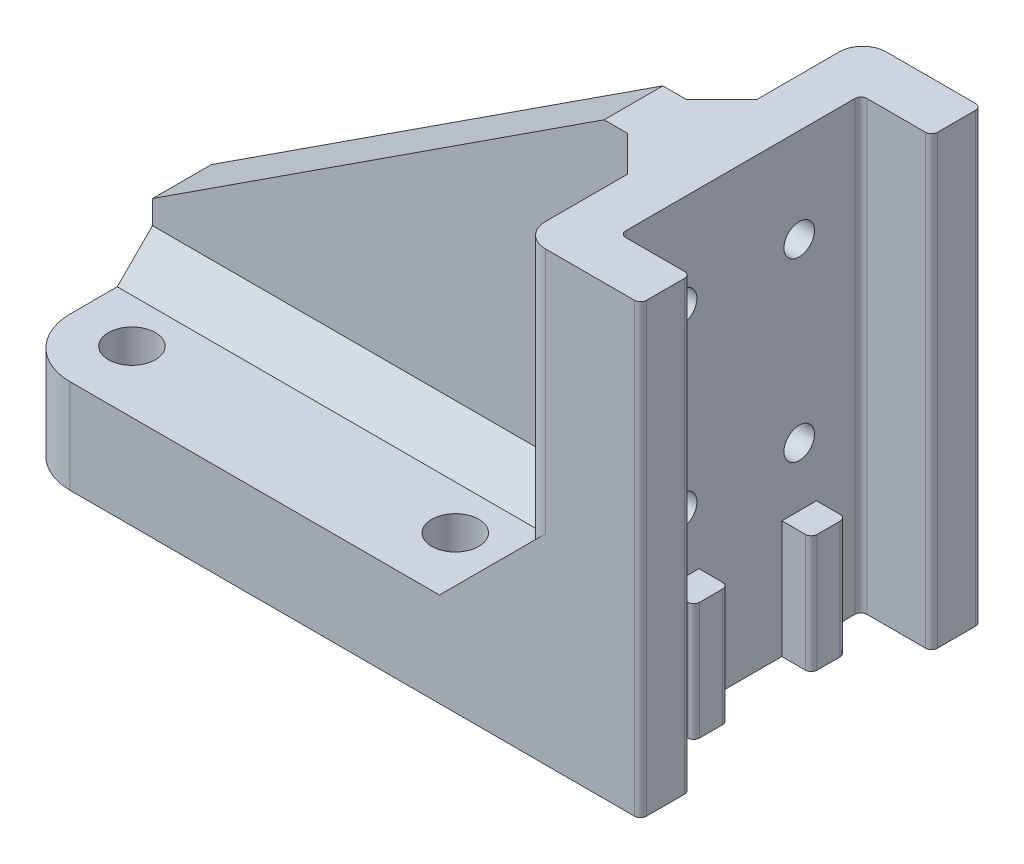
SolidWorks part; units mm, degrees
ref_plane "Plan de face" through (0, 0, 0) normal (0, 0, 1) x (1, 0, 0)
ref_plane "Plan de dessus" through (0, 0, 0) normal (0, 1, 0) x (1, 0, 0)
ref_plane "Plan de droite" through (0, 0, 0) normal (1, 0, 0) x (0, 0, -1)
sketch "Esquisse1" plane through (0, 0, 0) normal (0, 1, 0) x (1, 0, 0)
  line L0 (0, 29) -> (0, 0) construction
  line L1 (37.5, 29) -> (-37.5, 29)
  line L2 (37.5, 29) -> (37.5, -29)
  line L3 (37.5, -29) -> (-37.5, -29)
  line L4 (-37.5, 29) -> (-37.5, -29)
  line L5 (37.5, 29) -> (-37.5, -29) construction
  line L6 (37.5, -29) -> (-37.5, 29) construction
  line L7 (0, 0) -> (37.5, 0) construction
  circle A0 centre (-27.5, 18.5) radius 4
  circle A1 centre (27.5, 18.5) radius 4
  circle A2 centre (27.5, -18.5) radius 4
  circle A3 centre (-27.5, -18.5) radius 4
  point P0 (0, 0)
  dimension "D3" = 8
  dimension "D1" = 75
  dimension "D2" = 58
  dimension "D4" = 55
  dimension "D5" = 37
extrude "Boss.-Extru.1" add sketch "Esquisse1" along normal blind 16
sketch "Esquisse2" plane through (37.5, 0, 0) normal (1, 0, 0) x (0, 0, -1)
  line L4 (-29, 0) -> (29, 0)
  line L5 (29, 0) -> (29, 16)
  line L6 (29, 16) -> (-29, 16)
  line L7 (-29, 16) -> (-29, 0)
  line L8 (-29, 0) -> (29, 0)
  line L9 (29, 0) -> (29, 16)
  line L10 (29, 16) -> (-29, 16)
  line L11 (-29, 16) -> (-29, 0)
  dimension "D1" = 0
extrude "Boss.-Extru.2" add sketch "Esquisse2" along normal blind 20
sketch "Esquisse3" plane through (0, 16, 0) normal (0, 1, 0) x (1, 0, 0)
  line L0 (-37.5, -29) -> (57.5, -29) construction
  line L1 (57.5, 29) -> (49.3095, 29)
  line L2 (57.5, 29) -> (57.5, -29)
  line L3 (57.5, -29) -> (49.3095, -29)
  line L4 (49.3095, 29) -> (49.3095, -29)
extrude "Boss.-Extru.3" add sketch "Esquisse3" along normal blind 60
sketch "Esquisse4" plane through (57.5, 0, 0) normal (1, 0, 0) x (0, 0, -1)
  line L0 (0, 76) -> (0, 0) construction
  line L1 (-29, 76) -> (29, 76) construction
  line L2 (-29, 0) -> (29, 0) construction
  line L3 (20.5, 76) -> (20.5, 0)
  line L4 (-29, 76) -> (-20.5, 76)
  line L5 (-29, 76) -> (-29, 0)
  line L6 (-29, 0) -> (-20.5, 0)
  line L7 (-20.5, 76) -> (-20.5, 0)
  line L8 (29, 0) -> (20.5, 0)
  line L9 (29, 76) -> (29, 0)
  line L10 (29, 76) -> (20.5, 76)
  dimension "D1" = 41
extrude "Boss.-Extru.4" add sketch "Esquisse4" along normal blind 12
sketch "Esquisse5" plane through (57.5, 0, 0) normal (1, 0, 0) x (0, 0, -1)
  line L0 (0, 76) -> (0, 0) construction
  line L1 (-20.5, 76) -> (20.5, 76) construction
  line L2 (-20.5, 0) -> (20.5, 0) construction
  line L7 (-10, 20) -> (-10, -4.3804) construction
  line L8 (-12.95, 20) -> (-12.95, 0)
  line L9 (-7.05, 20) -> (-7.05, 0)
  line L10 (10, 20) -> (10, -4.3804) construction
  line L13 (7.05, 20) -> (7.05, 0)
  line L14 (12.95, 0) -> (7.05, 0)
  line L15 (12.95, 20) -> (12.95, 0)
  line L16 (12.95, 20) -> (7.05, 20)
  line L17 (-12.95, 20) -> (-7.05, 20)
  line L18 (-12.95, 0) -> (-7.05, 0)
  dimension "D1" = 5.9
  dimension "D2" = 20
  dimension "D3" = 20
extrude "Boss.-Extru.5" add sketch "Esquisse5" along normal blind 5
sketch "Esquisse6" plane through (49.3095, 0, 0) normal (-1, 0, 0) x (0, 0, 1)
  line L0 (0, 76) -> (0, 16) construction
  line L1 (-29, 76) -> (29, 76) construction
  line L2 (-29, 16) -> (29, 16) construction
  line L4 (5, 16) -> (-5, 16)
  line L5 (5, 16) -> (5, 76)
  line L6 (5, 76) -> (-5, 76)
  line L7 (-5, 16) -> (-5, 76)
  line L8 (5, 16) -> (-5, 76) construction
  line L9 (5, 76) -> (-5, 16) construction
  point P6 (0, 46)
  dimension "D1" = 10
extrude "Boss.-Extru.6" add sketch "Esquisse6" along normal up to surface (86.8095 mm away) up to face at (-37.5, 8, 0)
sketch "Esquisse7" plane through (49.3095, 0, 0) normal (-1, 0, 0) x (0, 0, 1)
  line L0 (-10, 76) -> (-10, 16) construction
  line L1 (-29, 76) -> (-5, 76) construction
  line L2 (-29, 16) -> (-5, 16) construction
  line L3 (0, 76) -> (0, 0) construction
  line L4 (-5, 76) -> (5, 76) construction
  line L5 (10, 76) -> (10, 16) construction
  circle A0 centre (-10, 60) radius 2.6
  circle A1 centre (-10, 30) radius 2.6
  circle A2 centre (10, 30) radius 2.6
  circle A3 centre (10, 60) radius 2.6
  dimension "D2" = 5.2
  dimension "D1" = 20
  dimension "D3" = 16
  dimension "D4" = 30
extrude "Enlèv. mat.-Extru.1" cut sketch "Esquisse7" against normal through all
sketch "Esquisse8" plane through (49.3095, 0, 0) normal (-1, 0, 0) x (0, 0, 1)
  circle A0 centre (-10, 60) radius 4.5
  circle A1 centre (-10, 30) radius 4.5
  circle A2 centre (10, 60) radius 4.5
  circle A3 centre (10, 30) radius 4.5
  dimension "D1" = 9
extrude "Enlèv. mat.-Extru.2" cut sketch "Esquisse8" against normal blind 3
sketch "Esquisse9" plane through (0, 0, -5) normal (0, 0, -1) x (-1, 0, 0)
  line L0 (-39.3095, 76) -> (37.5, 26)
  line L1 (37.5, 76) -> (-49.3095, 76) construction
  line L2 (37.5, 16) -> (37.5, 76) construction
  line L3 (37.5, 26) -> (37.5, 76)
  line L4 (37.5, 76) -> (-39.3095, 76)
  dimension "D1" = 10
  dimension "D2" = 10
extrude "Enlèv. mat.-Extru.3" cut sketch "Esquisse9" against normal through all
chamfer "Chanfrein1" distance 14 angle 45 2 edges at (49.3095, 16, 17) (49.3095, 16, -17)
chamfer "Chanfrein2" distance 6 angle 45 2 edges at (-1.0952, 16, 5) (-1.0952, 16, -5)
chamfer "Chanfrein3" distance 6 angle 45 2 edges at (49.3095, 53, 5) (49.3095, 53, -5)
fillet "Congé1" radius 10 2 edges at (-37.5, 8, 29) (-37.5, 8, -29)
fillet "Congé2" radius 4 2 edges at (49.3095, 53, 29) (49.3095, 53, -29)
fillet "Congé3" radius 1 4 edges at (69.5, 38, -29) (69.5, 38, -20.5) (69.5, 38, 20.5) (69.5, 38, 29)
fillet "Congé4" radius 1 6 edges at (57.5, 38, -20.5) (57.5, 38, 20.5) (62.5, 10, -12.95) (62.5, 10, -7.05) (62.5, 10, 7.05) (62.5, 10, 12.95)
